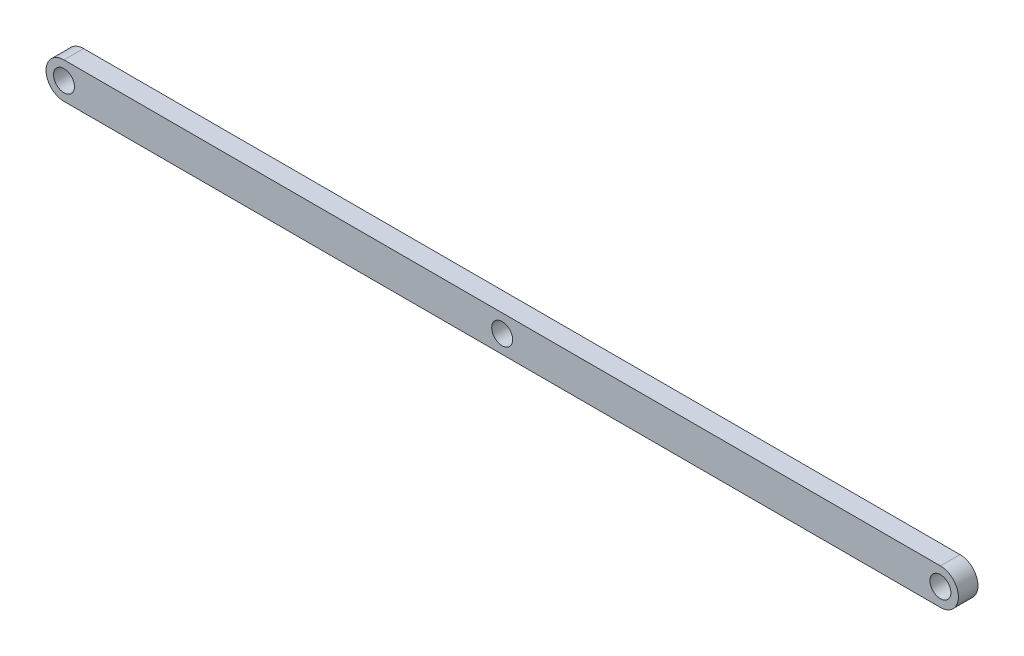
SolidWorks part; units mm, degrees
ref_plane "前基準面" through (0, 0, 0) normal (0, 0, 1) x (1, 0, 0)
ref_plane "上基準面" through (0, 0, 0) normal (0, 1, 0) x (1, 0, 0)
ref_plane "右基準面" through (0, 0, 0) normal (1, 0, 0) x (0, 0, -1)
sketch "草圖1" plane through (0, 0, 0) normal (0, 0, 1) x (1, 0, 0)
  line L0 (-41.9264, 0) -> (92.0736, 0) construction
  line L1 (-41.9264, 2.75) -> (92.0736, 2.75)
  line L2 (-41.9264, -2.75) -> (92.0736, -2.75)
  arc A0 (-41.9264, 2.75) -> (-41.9264, -2.75) centre (-41.9264, 0) ccw
  arc A1 (92.0736, -2.75) -> (92.0736, 2.75) centre (92.0736, 0) ccw
  circle A2 centre (92.0736, 0) radius 1.6
  circle A3 centre (-41.9264, 0) radius 1.6
  circle A4 centre (25.0736, 0) radius 1.6
  point P3 (25.0736, 0)
  dimension "D3" = 3.2
  dimension "D4" = 3.2
  dimension "D5" = 3.2
  dimension "D1" = 134
  dimension "D2" = 5.5
extrude "填料-伸長1" add sketch "草圖1" along normal blind 3
